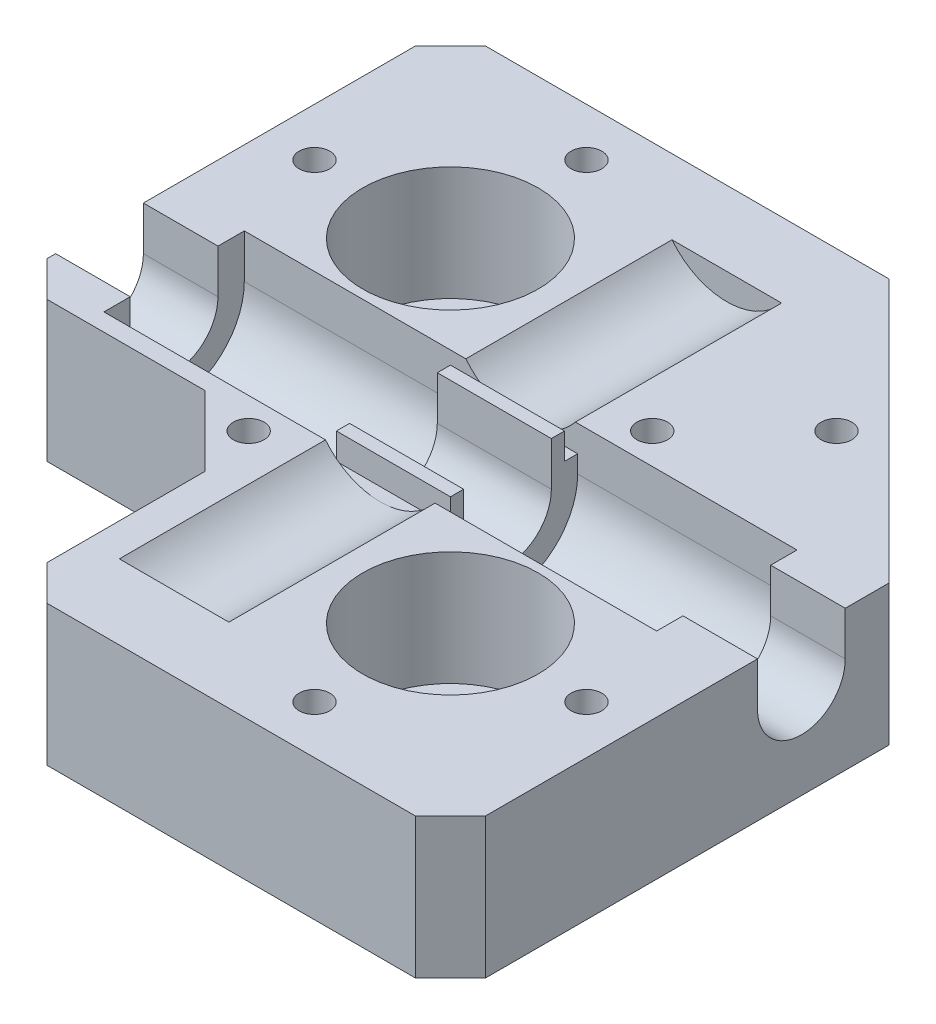
SolidWorks part; units mm, degrees
ref_plane "Front Plane" through (0, 0, 0) normal (0, 0, 1) x (1, 0, 0)
ref_plane "Top Plane" through (0, 0, 0) normal (0, 1, 0) x (1, 0, 0)
ref_plane "Right Plane" through (0, 0, 0) normal (1, 0, 0) x (0, 0, -1)
sketch "Sketch1" plane through (0, 0, 0) normal (0, 1, 0) x (1, 0, 0)
  line L1 (-40, -40) -> (40, -40)
  line L2 (-40, -40) -> (-40, 40)
  line L3 (-40, 40) -> (40, 40)
  line L4 (40, -40) -> (40, 40)
  line L5 (-40, -40) -> (40, 40) construction
  line L6 (-40, 40) -> (40, -40) construction
  point P0 (0, 0)
  dimension "D1" = 80
  dimension "D2" = 80
extrude "Boss-Extrude1" add sketch "Sketch1" against normal blind 16
sketch "Sketch2" plane through (0, 0, 0) normal (0, 1, 0) x (1, 0, 0)
  circle A0 centre (-11.5, -11.5) radius 1.75
  circle A1 centre (11.5, 11.5) radius 1.75
  circle A2 centre (22, 22) radius 1.75
  circle A3 centre (19, -34.5) radius 1.75
  circle A4 centre (34.5, -19) radius 1.75
  circle A5 centre (-34.5, 19) radius 1.75
  circle A6 centre (-19, 34.5) radius 1.75
  point P14 (0, 0)
  point P20 (0, 0)
  dimension "D1" = 3.5
  dimension "D2" = 3.5
  dimension "D3" = 3.5
  dimension "D4" = 3.5
  dimension "D5" = 3.5
  dimension "D6" = 3.5
  dimension "D7" = 3.5
  dimension "D8" = 11.5
  dimension "D9" = 11.5
  dimension "D10" = 11.5
  dimension "D11" = 11.5
  dimension "D12" = 22
  dimension "D13" = 22
  dimension "D14" = 34.5
  dimension "D15" = 34.5
  dimension "D16" = 19
  dimension "D17" = 19
  dimension "D18" = 34.5
  dimension "D19" = 19
  dimension "D20" = 19
  dimension "D21" = 34.5
extrude "Cut-Extrude1" cut sketch "Sketch2" against normal through all both and the other way through all
sketch "Sketch3" plane through (0, 0, 0) normal (0, 1, 0) x (1, 0, 0)
  line L1 (31.5, -8) -> (6.5, -8)
  line L2 (31.5, -8) -> (31.5, 8)
  line L3 (31.5, 8) -> (6.5, 8)
  line L4 (6.5, -8) -> (6.5, 8)
  line L5 (31.5, -8) -> (6.5, 8) construction
  line L6 (31.5, 8) -> (6.5, -8) construction
  line L7 (-6.5, -8) -> (-31.5, -8)
  line L8 (-6.5, -8) -> (-6.5, 8)
  line L9 (-6.5, 8) -> (-31.5, 8)
  line L10 (-31.5, -8) -> (-31.5, 8)
  line L11 (-6.5, -8) -> (-31.5, 8) construction
  line L12 (-6.5, 8) -> (-31.5, -8) construction
  point P0 (19, 0)
  point P5 (-19, 0)
  dimension "D1" = 16
  dimension "D2" = 0
  dimension "D3" = 25
  dimension "D4" = 19
  dimension "D5" = 25
  dimension "D6" = 16
  dimension "D7" = 0
  dimension "D8" = 19
extrude "Cut-Extrude2" cut sketch "Sketch3" against normal blind 13
fillet "Fillet1" radius 8 4 edges at (19, -13, 8) (19, -13, -8) (-19, -13, 8) (-19, -13, -8)
sketch "Sketch4" plane through (0, 0, 0) normal (0, 1, 0) x (1, 0, 0)
  line L1 (-8, -31.5) -> (8, -31.5)
  line L2 (-8, -31.5) -> (-8, -6.5)
  line L3 (-8, -6.5) -> (8, -6.5)
  line L4 (8, -31.5) -> (8, -6.5)
  line L5 (-8, -31.5) -> (8, -6.5) construction
  line L6 (-8, -6.5) -> (8, -31.5) construction
  line L7 (-8, 6.5) -> (8, 6.5)
  line L8 (-8, 6.5) -> (-8, 31.5)
  line L9 (-8, 31.5) -> (8, 31.5)
  line L10 (8, 6.5) -> (8, 31.5)
  point P0 (0, -19)
  dimension "D1" = 16
  dimension "D2" = 0
  dimension "D3" = 25
  dimension "D4" = 19
  dimension "D5" = 25
  dimension "D6" = 6.5
extrude "Cut-Extrude3" cut sketch "Sketch4" against normal blind 3
sketch3d "3DSketch1" [suppressed]
  line L1 (-8, -3, 8) -> (8, -3, 8)
  line L2 (-8, -3, 8) -> (-8, 0, 8)
  line L3 (-8, 0, 8) -> (8, 0, 8)
  line L4 (8, -3, 8) -> (8, 0, 8)
  circle A0 centre (0, 5, 8) radius 8
  point P2 (0, 5, 16)
  point P3 (0, 0, 8)
  point P5 (0, 0, 8)
  dimension "D4" = 16
  dimension "D1" = 8
  dimension "D2" = 0
  dimension "D3" = 5
sketch "Sketch5" plane through (0, 0, 31.5) normal (0, 0, -1) x (-1, 0, 0)
  line L0 (8, -3) -> (-8, -3) construction
  line L5 (8, 0) -> (-8, 0)
  line L6 (-8, 0) -> (-8, -3)
  line L7 (-8, -3) -> (8, -3)
  line L8 (8, -3) -> (8, 0)
  line L9 (8, 0) -> (-8, 0)
  line L10 (-8, 0) -> (-8, -3)
  line L11 (-8, -3) -> (8, -3)
  line L12 (8, -3) -> (8, 0)
  circle A0 centre (0, 5) radius 8
  line M6 (8, 0) -> (-8, 0)
  line M7 (-8, 0) -> (-8, -3)
  line M8 (-8, -3) -> (8, -3)
  line M9 (8, -3) -> (8, 0)
  dimension "D2" = 16
  dimension "D1" = 8
  dimension "D3" = 0
extrude "Boss-Extrude2" add sketch "Sketch5" along normal blind 23.5 contours A0 M6 M7 M8 | A0 L11 M9 M6 region at (-5.8898, -1.8317, 31.5) region at (5.8898, -1.8317, 31.5)
mirror "Mirror1" about plane through (0, 0, 0) normal (0, 0, 1) of "Boss-Extrude2"
sketch "Sketch6" plane through (0, 0, 0) normal (1, 0, 0) x (0, 0, -1)
  line L1 (5, -5) -> (-5, -5)
  line L2 (5, -5) -> (5, 0)
  line L3 (5, 0) -> (-5, 0)
  line L4 (-5, -5) -> (-5, 0)
  circle A0 centre (0, -5) radius 5
  dimension "D2" = 10
  dimension "D1" = 5
extrude "Cut-Extrude4" cut sketch "Sketch6" against normal through all both and the other way through all contours L1 A0 | A0 L3 L4 | A0 L2 L3 | L1 A0 region at (0, -7.1221, 0) region at (0, -1.1168, -3.8832) region at (0, -2.8779, 0) region at (0, -1.1168, 3.8832)
sketch "Sketch7" plane through (0, 0, 0) normal (0, 1, 0) x (1, 0, 0)
  circle A0 centre (19, -19) radius 10
  circle A1 centre (-19, 19) radius 10
  point P4 (0, 0)
  dimension "D5" = 20
  dimension "D6" = 20
  dimension "D1" = 19
  dimension "D2" = 19
  dimension "D3" = 19
  dimension "D4" = 19
extrude "Cut-Extrude5" cut sketch "Sketch7" against normal through all both and the other way through all
sketch "Sketch8" plane through (0, 0, -6.5) normal (0, 0, -1) x (-1, 0, 0)
  line L4 (6.5, 0) -> (-6.5, 0)
  line L5 (-6.5, 0) -> (-6.5, -3)
  line L6 (-6.5, -3) -> (6.5, -3)
  line L7 (6.5, -3) -> (6.5, 0)
  line L8 (6.5, 0) -> (-6.5, 0)
  line L9 (-6.5, 0) -> (-6.5, -3)
  line L10 (-6.5, -3) -> (6.5, -3)
  line L11 (6.5, -3) -> (6.5, 0)
  arc A0 (0, -3) -> (6.245, 0) centre (0, 5) ccw construction
  arc A1 (-6.245, 0) -> (0, -3) centre (0, 5) ccw construction
  arc A2 (0, -3) -> (6.245, 0) centre (0, 5) ccw
  arc A3 (-6.245, 0) -> (0, -3) centre (0, 5) ccw
  line M5 (6.5, 0) -> (-6.5, 0)
  line M6 (-6.5, 0) -> (-6.5, -3)
  line M7 (-6.5, -3) -> (6.5, -3)
  line M8 (6.5, -3) -> (6.5, 0)
  dimension "D1" = 0
extrude "Boss-Extrude3" [suppressed] add sketch "Sketch8" along normal blind 1.5 contours A3 M5 M6 M7 | A2 L10 M8 M5
mirror "Mirror2" [suppressed] about plane through (0, 0, 0) normal (0, 0, 1)
sketch "Sketch9" plane through (0, 0, 0) normal (0, 1, 0) x (1, 0, 0)
  line L0 (-10, -18) -> (-18, -10)
  line L1 (-40, -40) -> (-10, -40)
  line L2 (-40, -40) -> (-40, -10)
  line L3 (-40, -10) -> (-10, -10)
  line L4 (-10, -40) -> (-10, -10)
  line L5 (-10, -10) -> (-18, -10)
  line L6 (-10, -10) -> (-10, -18)
  line L7 (-10, -18) -> (-18, -18)
  line L8 (-18, -10) -> (-18, -18)
  dimension "D1" = 30
  dimension "D2" = 30
  dimension "D3" = 8
  dimension "D4" = 8
extrude "Cut-Extrude6" cut sketch "Sketch9" against normal through all both and the other way through all contours L0 L8 L7 | L8 L3 L2 L1 L4 L7 region at (-15.3333, 0, 15.3333) region at (-25.8421, 0, 25.8421)
chamfer "Chamfer1" distance 4 angle 45 4 edges at (40, -8, 40) (-40, -8, -40) (-40, -8, 10) (-10, -8, 40)
chamfer "Chamfer2" distance 30 angle 45 1 edges at (40, -8, -40)
sketch "Sketch11" plane through (0, -16, 0) normal (0, -1, 0) x (1, 0, 0)
  circle A0 centre (-19, -19) radius 10 construction
  circle A1 centre (19, 19) radius 10 construction
  circle A2 centre (-19, -19) radius 10
  circle A3 centre (19, 19) radius 10
  circle A4 centre (-19, -19) radius 4.25
  circle A5 centre (19, 19) radius 4.25
  dimension "D1" = 8.5
  dimension "D2" = 8.5
extrude "Boss-Extrude4" add sketch "Sketch11" against normal blind 3
sketch "Sketch12" plane through (0, -16, 0) normal (0, -1, 0) x (1, 0, 0)
  circle A0 centre (0, 0) radius 4
  circle A1 centre (16.75, -16.75) radius 4
  dimension "D1" = 8
  dimension "D4" = 8
  dimension "D2" = 16.75
  dimension "D3" = 16.75
extrude "Cut-Extrude7" cut sketch "Sketch12" against normal blind 5
sketch "Sketch13" plane through (0, -16, 0) normal (0, -1, 0) x (1, 0, 0)
  circle A0 centre (22, -22) radius 1.75 construction
  circle A1 centre (11.5, -11.5) radius 1.75 construction
  circle A2 centre (-19, -34.5) radius 1.75 construction
  circle A3 centre (-34.5, -19) radius 1.75 construction
  circle A4 centre (-11.5, 11.5) radius 1.75 construction
  circle A5 centre (34.5, 19) radius 1.75 construction
  circle A6 centre (19, 34.5) radius 1.75 construction
  circle A7 centre (22, -22) radius 1.75
  circle A8 centre (11.5, -11.5) radius 1.75
  circle A9 centre (-19, -34.5) radius 1.75
  circle A10 centre (-34.5, -19) radius 1.75
  circle A11 centre (-11.5, 11.5) radius 1.75
  circle A12 centre (34.5, 19) radius 1.75
  circle A13 centre (19, 34.5) radius 1.75
  circle A14 centre (19, 34.5) radius 3
  circle A15 centre (34.5, 19) radius 3
  circle A16 centre (-11.5, 11.5) radius 3
  circle A17 centre (-34.5, -19) radius 3
  circle A18 centre (-19, -34.5) radius 3
  circle A19 centre (11.5, -11.5) radius 3
  circle A20 centre (22, -22) radius 3
  dimension "D1" = 6
  dimension "D2" = 6
  dimension "D3" = 6
  dimension "D4" = 6
  dimension "D5" = 6
  dimension "D6" = 6
  dimension "D7" = 6
extrude "Cut-Extrude8" cut sketch "Sketch13" against normal blind 10
